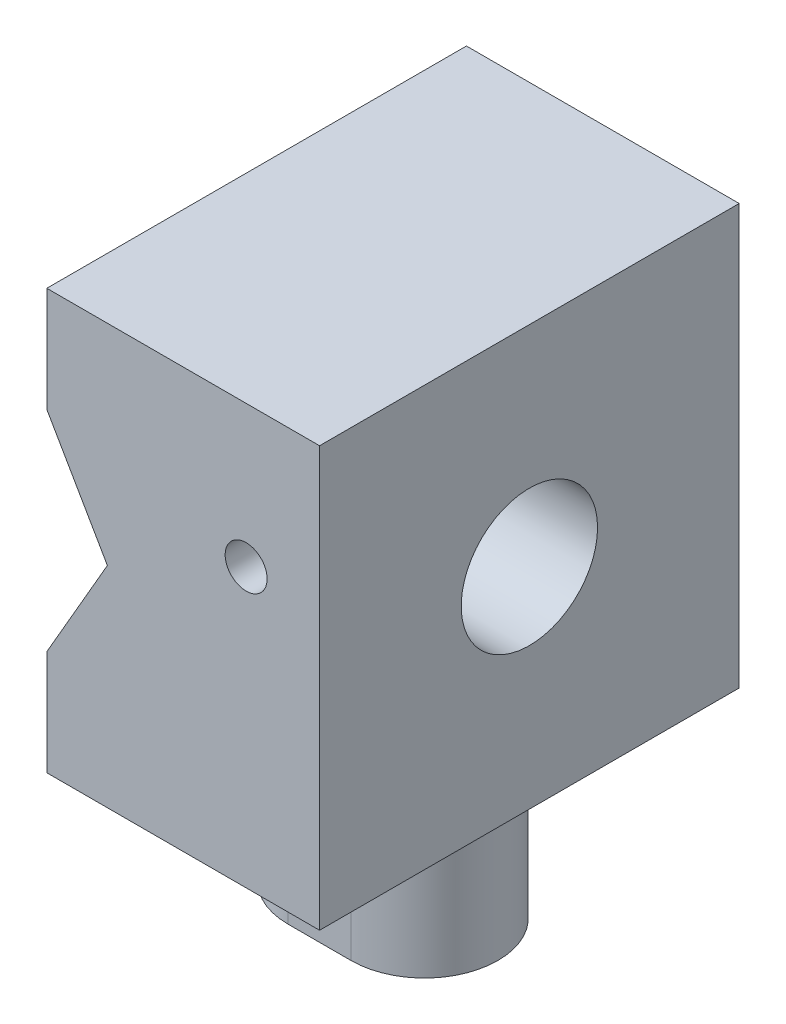
SolidWorks part; units mm, degrees
material "AISI Aço-ferramenta tipo A2"
ref_plane "Plano frontal" through (0, 0, 0) normal (0, 0, 1) x (1, 0, 0)
ref_plane "Plano superior" through (0, 0, 0) normal (0, 1, 0) x (1, 0, 0)
ref_plane "Plano direito" through (0, 0, 0) normal (1, 0, 0) x (0, 0, -1)
sketch "Esboço1" plane through (0, 0, 0) normal (0, 0, 1) x (1, 0, 0)
  line L0 (-11.8649, 0) -> (14.1351, 0)
  line L1 (14.1351, 0) -> (14.1351, 40)
  line L2 (-11.8649, 40) -> (14.1351, 40)
  line L3 (-11.8649, 40) -> (-11.8649, 30)
  line L5 (-6.0914, 20) -> (-11.8649, 10)
  line L6 (-11.8649, 10) -> (-11.8649, 0)
  line L7 (-11.8649, 30) -> (-6.0914, 20)
  line L8 (-11.8649, 30) -> (-11.8649, 10) construction
  dimension "D1" = 10
  dimension "D2" = 40
  dimension "D3" = 26
  dimension "D4" = 10
  dimension "D5" = 120
  dimension "D6" = 26
extrude "Ressalto-extrusão1" add sketch "Esboço1" against normal blind 40
sketch "Esboço2" plane through (14.1351, 0, 0) normal (1, 0, 0) x (0, 0, -1)
  line L0 (40, 40) -> (0, 40) construction
  circle A0 centre (20, 20) radius 6.5
  point P7 (20, 40)
  dimension "D1" = 13
extrude "Corte-extrusão1" cut sketch "Esboço2" against normal blind 19
chamfer "Chanfro1" distance 4 distance2 6.5 1 edges at (-4.8649, 20, -26.5) first distance on face at (-4.8649, 20, -26.5)
sketch "Esboço3" plane through (0, 0, 0) normal (0, 0, 1) x (1, 0, 0)
  line L0 (14.1351, 40) -> (-11.8649, 40) construction
  line L1 (14.1351, 0) -> (14.1351, 40) construction
  circle A0 centre (7.1351, 26.5) radius 2
  dimension "D1" = 13.5
  dimension "D2" = 7
extrude "Corte-extrusão2" cut sketch "Esboço3" against normal through all
sketch "Esboço4" plane through (0, 0, 0) normal (0, -1, 0) x (1, 0, 0)
  line L0 (-1.8649, -20) -> (4.1351, -20) construction
  line L1 (-1.8649, -13) -> (4.1351, -13)
  line L2 (-1.8649, -27) -> (4.1351, -27)
  line L4 (-11.8649, -40) -> (14.1351, -40) construction
  line L5 (-11.8649, -40) -> (-11.8649, 0) construction
  arc A0 (-1.8649, -13) -> (-1.8649, -27) centre (-1.8649, -20) ccw
  arc A1 (4.1351, -27) -> (4.1351, -13) centre (4.1351, -20) ccw
  point P2 (1.1351, -20)
  dimension "D1" = 6
  dimension "D2" = 14
  dimension "D3" = 20
  dimension "D4" = 13
extrude "Ressalto-extrusão2" add sketch "Esboço4" along normal blind 14
sketch "Esboço5" plane through (0, -14, 0) normal (0, -1, 0) x (1, 0, 0)
  line L0 (-11.8649, -40) -> (-11.8649, 0) construction
  line L1 (-11.8649, -40) -> (14.1351, -40) construction
  circle A0 centre (1.1351, -20) radius 3.9688
  dimension "D3" = 7.9375
  dimension "D1" = 13
  dimension "D2" = 20
hole_wizard "Broca de rosquear para tarraxa de 5/16-181" positions "Esboço6" profile "Esboço7" hole size "5/16-18" standard "Ansi Inch"
sketch "Esboço6" plane through (0, -14, 0) normal (0, -1, 0) x (-1, 0, 0)
  point P0 (-1.1351, 20)
sketch "Esboço7" plane through (1.1351, -14, -20) normal (1, 0, 0) x (0, 0, -1)
  line L0 (0, 0) -> (0, 14.9611)
  line L1 (0, 14.9611) -> (3.2639, 13)
  line L2 (3.2639, 13) -> (3.2639, 0)
  line L5 (3.2639, 0) -> (0, 0)
  line L10 (0, 14.9611) -> (-3.2639, 13) construction
  line L11 (0, -6.35) -> (0, 107.95) construction
  dimension "Hole Dia." = 6.5278
  dimension "Hole Depth" = 13
  dimension "Drill Angle" = 118
